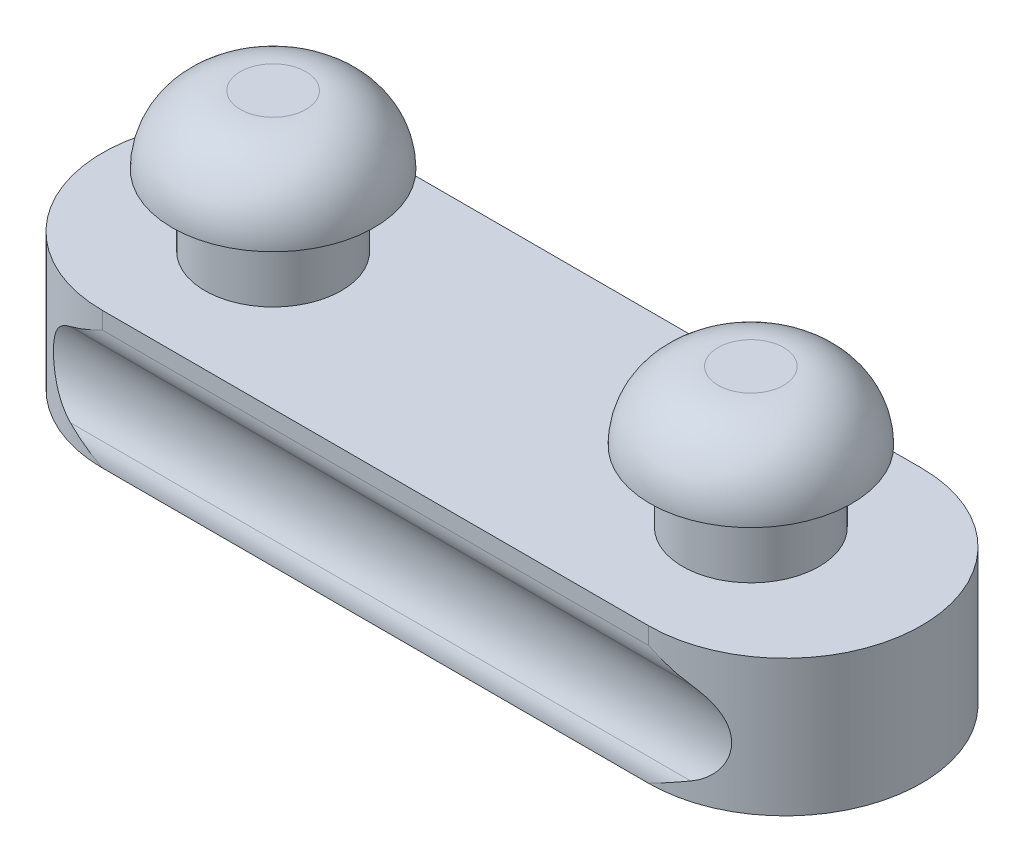
SolidWorks part; units mm, degrees
ref_plane "Front Plane" through (0, 0, 0) normal (0, 0, 1) x (1, 0, 0)
ref_plane "Top Plane" through (0, 0, 0) normal (0, 1, 0) x (1, 0, 0)
ref_plane "Right Plane" through (0, 0, 0) normal (1, 0, 0) x (0, 0, -1)
sketch "Sketch1" plane through (0, 0, 0) normal (0, 1, 0) x (1, 0, 0)
  line L0 (-11.1125, 0) -> (11.1125, 0) construction
  line L1 (-12.7, 6.35) -> (12.7, 6.35)
  line L3 (-12.7, -6.35) -> (12.7, -6.35)
  line L5 (-12.7, 6.35) -> (12.7, -6.35) construction
  line L6 (-12.7, -6.35) -> (12.7, 6.35) construction
  circle A0 centre (-11.1125, 0) radius 3.175
  circle A1 centre (11.1125, 0) radius 3.175
  arc A2 (-12.7, 6.35) -> (-12.7, -6.35) centre (-12.7, 0) ccw
  arc A3 (12.7, -6.35) -> (12.7, 6.35) centre (12.7, 0) ccw
  point P0 (0, 0)
  point P11 (0, 6.35)
  point P13 (0, 0)
  point P14 (-19.05, 0)
  point P15 (19.05, 0)
  dimension "D4" = 6.35
  dimension "D1" = 22.225
  dimension "D2" = 12.7
  dimension "D3" = 38.1
extrude "Boss-Extrude1" add sketch "Sketch1" along normal blind 6.35 contours L3 A3 L1 A2 A0 A1 | A0 | A1 region at (0, 0, 0) region at (-11.1125, 0, 0) region at (11.1125, 0, 0)
extrude "Boss-Extrude2" add sketch "Sketch1<4>" along normal blind 3.302 from surface contours A0 | A1 region at (-11.1125, 0, 0) region at (11.1125, 0, 0) starting at face at (0, 6.35, 0)
sketch "Sketch1<4>" plane through (0, 0, 0) normal (0, 1, 0) x (1, 0, 0) same geometry as "Sketch1"
sketch "Sketch2" plane through (0, 9.652, 0) normal (0, 1, 0) x (1, 0, 0)
  circle A0 centre (-11.1125, 0) radius 4.699
  circle A1 centre (11.1125, 0) radius 4.699
  dimension "D1" = 9.398
extrude "Boss-Extrude3" add sketch "Sketch2" along normal blind 3.175
sketch "Sketch3" plane through (0, 0, 0) normal (1, 0, 0) x (0, 0, -1)
  line L0 (-6.35, 0) -> (6.35, 0) construction
  line L2 (6.35, 6.35) -> (6.35, 5.5563)
  line L3 (6.35, 6.35) -> (6.35, 0) construction
  line L4 (6.35, 6.35) -> (6.35, 0)
  line L5 (0, 7.0548) -> (0, -7.0548) construction
  line L6 (-6.35, 6.35) -> (-6.35, 5.5563)
  line L7 (-6.35, 6.35) -> (-6.35, 0)
  arc A0 (6.35, 5.5563) -> (6.1104, 4.7176) centre (4.7625, 5.5562) cw
  arc A1 (6.1104, 4.7176) -> (5.5563, 2.7781) centre (9.2273, 2.7781) ccw
  arc A2 (5.5563, 2.7781) -> (6.1104, 0.8387) centre (9.2273, 2.7781) ccw
  arc A3 (6.1104, 0.8387) -> (6.35, 0) centre (4.7625, 0) cw
  arc A4 (-6.1104, 0.8387) -> (-6.35, 0) centre (-4.7625, 0) ccw
  arc A5 (-5.5563, 2.7781) -> (-6.1104, 0.8387) centre (-9.2273, 2.7781) cw
  arc A6 (-6.35, 5.5563) -> (-6.1104, 4.7176) centre (-4.7625, 5.5562) ccw
  arc A7 (-6.1104, 4.7176) -> (-5.5563, 2.7781) centre (-9.2273, 2.7781) cw
  dimension "D3" = 1.5875
  dimension "D1" = 0.7937
  dimension "D2" = 0.7937
extrude "Cut-Extrude1" cut sketch "Sketch3" against normal mid plane 40.64 contours A2 A3 L4 A0 A1 | A7 A6 L7 A4 A5 region at (0, 2.7781, -6.0342) region at (0, 2.7781, 6.0342)
fillet "Fillet1" radius 3.175 2 edges at (11.1125, 12.827, 4.699) (-11.1125, 12.827, 4.699)
equation "\"WallThickness\"=0.125"
equation "\"D1@Boss-Extrude2\"=\"WallThickness\"+.005"
